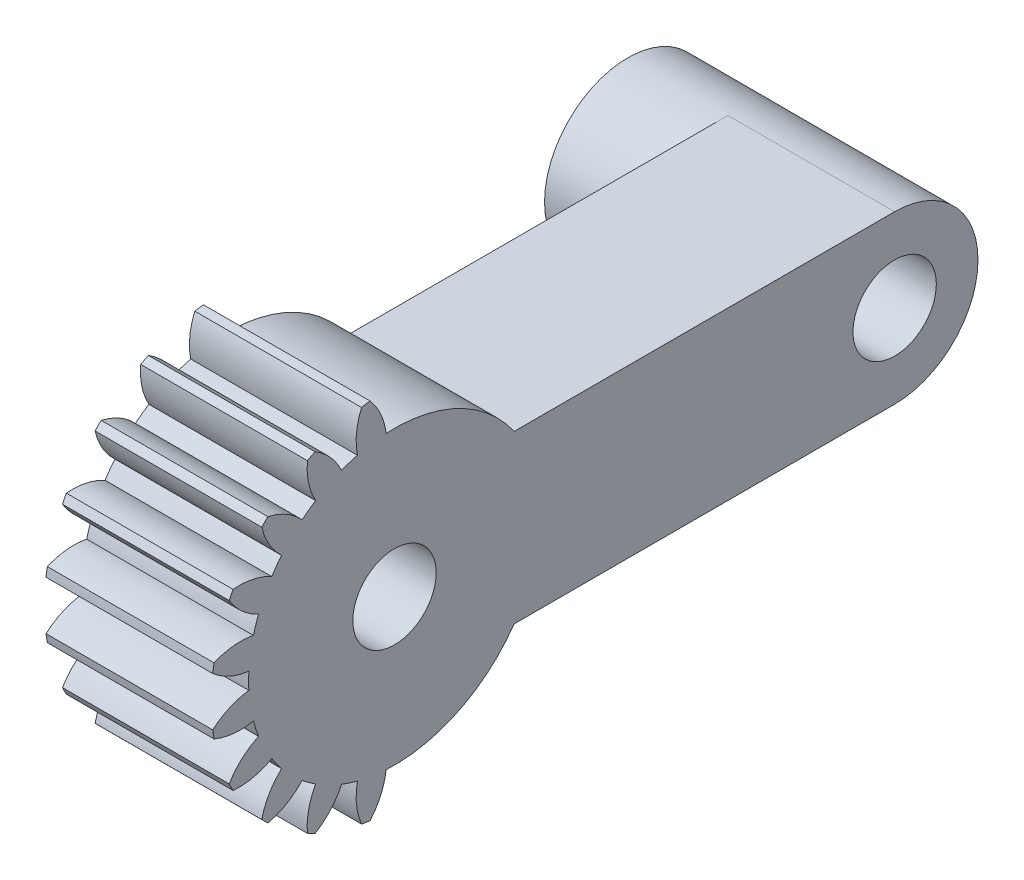
SolidWorks part; units mm, degrees
ref_plane "Front Plane" through (0, 0, 0) normal (0, 0, 1) x (1, 0, 0)
ref_plane "Top Plane" through (0, 0, 0) normal (0, 1, 0) x (1, 0, 0)
ref_plane "Right Plane" through (0, 0, 0) normal (1, 0, 0) x (0, 0, -1)
ref_plane "Plane1" through (4.0439, 0, 0) normal (1, 0, 0) x (0, 0, -1)
sketch "Sketch1" plane through (4.0439, 0, 0) normal (1, 0, 0) x (0, 0, -1)
  circle A0 centre (0.8725, -1.1221) radius 2.5
  arc A1 (-10.0295, 0.3429) -> (-7.8622, -0.6222) centre (-7.392, 3.3501) ccw
  arc A2 (-7.8622, -0.6222) -> (-7.8622, -1.622) centre (0.8725, -1.1221) ccw
  arc A3 (-7.8622, -1.622) -> (-10.0295, -2.587) centre (-7.392, -5.5943) ccw
  arc A4 (-10.0295, -2.587) -> (-9.9487, -3.0977) centre (0.8725, -1.1221) ccw
  arc A5 (-9.9487, -3.0977) -> (-7.5892, -3.3458) centre (-8.3695, 0.5774) ccw
  arc A6 (-7.5892, -3.3458) -> (-7.2802, -4.2967) centre (0.8725, -1.1221) ccw
  arc A7 (-7.2802, -4.2967) -> (-9.0433, -5.8842) centre (-5.6055, -7.9292) ccw
  arc A8 (-9.0433, -5.8842) -> (-8.8085, -6.3449) centre (0.8725, -1.1221) ccw
  arc A9 (-8.8085, -6.3449) -> (-6.4879, -5.8518) centre (-8.4423, -2.3617) ccw
  arc A10 (-6.4879, -5.8518) -> (-5.9002, -6.6607) centre (0.8725, -1.1221) ccw
  arc A11 (-5.9002, -6.6607) -> (-7.0864, -8.7153) centre (-3.185, -9.5979) ccw
  arc A12 (-7.0864, -8.7153) -> (-6.7207, -9.0809) centre (0.8725, -1.1221) ccw
  arc A13 (-6.7207, -9.0809) -> (-4.6661, -7.8948) centre (-7.6033, -5.1795) ccw
  arc A14 (-4.6661, -7.8948) -> (-3.8572, -8.4825) centre (0.8725, -1.1221) ccw
  arc A15 (-3.8572, -8.4825) -> (-4.3504, -10.8031) centre (-0.3672, -10.4369) ccw
  arc A16 (-4.3504, -10.8031) -> (-3.8897, -11.0378) centre (0.8725, -1.1221) ccw
  arc A17 (-3.8897, -11.0378) -> (-2.3022, -9.2748) centre (-5.9347, -7.6001) ccw
  arc A18 (-2.3022, -9.2748) -> (-1.3512, -9.5838) centre (0.8725, -1.1221) ccw
  arc A19 (-1.3512, -9.5838) -> (-1.1032, -11.9432) centre (2.5719, -10.3641) ccw
  arc A20 (-1.1032, -11.9432) -> (-0.5925, -12.0241) centre (0.8725, -1.1221) ccw
  arc A21 (-0.5925, -12.0241) -> (0.3725, -9.8568) centre (-3.5997, -9.3866) ccw
  arc A22 (0.3725, -9.8568) -> (1.3724, -9.8568) centre (0.8725, -1.1221) ccw
  arc A23 (1.3724, -9.8568) -> (2.3374, -12.0241) centre (5.3447, -9.3866) ccw
  arc A24 (2.3374, -12.0241) -> (2.8481, -11.9432) centre (0.8725, -1.1221) ccw
  arc A25 (2.8481, -11.9432) -> (3.0962, -9.5838) centre (-0.827, -10.3641) ccw
  arc A26 (3.0962, -9.5838) -> (4.0471, -9.2748) centre (0.8725, -1.1221) ccw
  arc A27 (4.0471, -9.2748) -> (5.6346, -11.0378) centre (7.6796, -7.6001) ccw
  arc A28 (5.6346, -11.0378) -> (6.0953, -10.8031) centre (0.8725, -1.1221) ccw
  arc A29 (6.0953, -10.8031) -> (5.6022, -8.4825) centre (2.1121, -10.4369) ccw
  arc A30 (5.6022, -8.4825) -> (6.411, -7.8948) centre (0.8725, -1.1221) ccw
  arc A31 (6.411, -7.8948) -> (8.4657, -9.0809) centre (9.3483, -5.1795) ccw
  arc A32 (8.4657, -9.0809) -> (8.8313, -8.7153) centre (0.8725, -1.1221) ccw
  arc A33 (8.8313, -8.7153) -> (7.6451, -6.6607) centre (4.9299, -9.5979) ccw
  arc A34 (7.6451, -6.6607) -> (8.2328, -5.8518) centre (0.8725, -1.1221) ccw
  arc A35 (8.2328, -5.8518) -> (10.5535, -6.3449) centre (10.1873, -2.3617) ccw
  arc A36 (10.5535, -6.3449) -> (10.7882, -5.8842) centre (0.8725, -1.1221) ccw
  arc A37 (10.7882, -5.8842) -> (9.0252, -4.2967) centre (7.3505, -7.9292) ccw
  arc A38 (9.0252, -4.2967) -> (9.3342, -3.3458) centre (0.8725, -1.1221) ccw
  arc A39 (9.3342, -3.3458) -> (11.6936, -3.0977) centre (10.1144, 0.5774) ccw
  arc A40 (11.6936, -3.0977) -> (11.7745, -2.587) centre (0.8725, -1.1221) ccw
  arc A41 (11.7745, -2.587) -> (9.6072, -1.622) centre (9.137, -5.5943) ccw
  arc A42 (9.6072, -1.622) -> (9.6072, -0.6222) centre (0.8725, -1.1221) ccw
  arc A43 (9.6072, -0.6222) -> (11.7745, 0.3429) centre (9.137, 3.3501) ccw
  arc A44 (11.7745, 0.3429) -> (11.6936, 0.8536) centre (0.8725, -1.1221) ccw
  arc A45 (11.6936, 0.8536) -> (9.3342, 1.1016) centre (10.1144, -2.8215) ccw
  arc A46 (9.3342, 1.1016) -> (9.0252, 2.0526) centre (0.8725, -1.1221) ccw
  arc A47 (9.0252, 2.0526) -> (10.7882, 3.6401) centre (7.3505, 5.6851) ccw
  arc A48 (10.7882, 3.6401) -> (10.5535, 4.1008) centre (0.8725, -1.1221) ccw
  arc A49 (10.5535, 4.1008) -> (8.2328, 3.6076) centre (10.1873, 0.1176) ccw
  arc A50 (8.2328, 3.6076) -> (7.6451, 4.4165) centre (0.8725, -1.1221) ccw
  arc A51 (7.6451, 4.4165) -> (8.8313, 6.4711) centre (4.9299, 7.3537) ccw
  arc A52 (8.8313, 6.4711) -> (8.4657, 6.8368) centre (0.8725, -1.1221) ccw
  arc A53 (8.4657, 6.8368) -> (6.411, 5.6506) centre (9.3483, 2.9353) ccw
  arc A54 (6.411, 5.6506) -> (5.6022, 6.2383) centre (0.8725, -1.1221) ccw
  arc A55 (5.6022, 6.2383) -> (6.0953, 8.5589) centre (2.1121, 8.1927) ccw
  arc A56 (6.0953, 8.5589) -> (5.6346, 8.7937) centre (0.8725, -1.1221) ccw
  arc A57 (5.6346, 8.7937) -> (4.0471, 7.0306) centre (7.6796, 5.3559) ccw
  arc A58 (4.0471, 7.0306) -> (3.0962, 7.3396) centre (0.8725, -1.1221) ccw
  arc A59 (3.0962, 7.3396) -> (2.8481, 9.6991) centre (-0.827, 8.1199) ccw
  arc A60 (2.8481, 9.6991) -> (2.3374, 9.7799) centre (0.8725, -1.1221) ccw
  arc A61 (2.3374, 9.7799) -> (1.3724, 7.6126) centre (5.3447, 7.1424) ccw
  arc A62 (1.3724, 7.6126) -> (0.3725, 7.6126) centre (0.8725, -1.1221) ccw
  arc A63 (0.3725, 7.6126) -> (-0.5925, 9.7799) centre (-3.5997, 7.1424) ccw
  arc A64 (-0.5925, 9.7799) -> (-1.1032, 9.6991) centre (0.8725, -1.1221) ccw
  arc A65 (-1.1032, 9.6991) -> (-1.3512, 7.3396) centre (2.5719, 8.1199) ccw
  arc A66 (-1.3512, 7.3396) -> (-2.3022, 7.0306) centre (0.8725, -1.1221) ccw
  arc A67 (-2.3022, 7.0306) -> (-3.8897, 8.7937) centre (-5.9347, 5.3559) ccw
  arc A68 (-3.8897, 8.7937) -> (-4.3504, 8.5589) centre (0.8725, -1.1221) ccw
  arc A69 (-4.3504, 8.5589) -> (-3.8572, 6.2383) centre (-0.3672, 8.1927) ccw
  arc A70 (-3.8572, 6.2383) -> (-4.6661, 5.6506) centre (0.8725, -1.1221) ccw
  arc A71 (-4.6661, 5.6506) -> (-6.7207, 6.8368) centre (-7.6033, 2.9353) ccw
  arc A72 (-6.7207, 6.8368) -> (-7.0864, 6.4711) centre (0.8725, -1.1221) ccw
  arc A73 (-7.0864, 6.4711) -> (-5.9002, 4.4165) centre (-3.185, 7.3537) ccw
  arc A74 (-5.9002, 4.4165) -> (-6.4879, 3.6076) centre (0.8725, -1.1221) ccw
  arc A75 (-6.4879, 3.6076) -> (-8.8085, 4.1008) centre (-8.4423, 0.1176) ccw
  arc A76 (-8.8085, 4.1008) -> (-9.0433, 3.6401) centre (0.8725, -1.1221) ccw
  arc A77 (-9.0433, 3.6401) -> (-7.2802, 2.0526) centre (-5.6055, 5.6851) ccw
  arc A78 (-7.2802, 2.0526) -> (-7.5892, 1.1016) centre (0.8725, -1.1221) ccw
  arc A79 (-7.5892, 1.1016) -> (-9.9487, 0.8536) centre (-8.3695, -2.8215) ccw
  arc A80 (-9.9487, 0.8536) -> (-10.0295, 0.3429) centre (0.8725, -1.1221) ccw
extrude "Boss-Extrude1" add sketch "Sketch1" against normal blind 10
sketch "Sketch2" plane through (4.0439, 0, 0) normal (1, 0, 0) x (0, 0, -1)
  line L0 (0.8725, -1.1221) -> (30.8725, -1.1221) construction
  line L1 (0.8725, 3.8779) -> (30.8725, 3.8779)
  line L2 (0.8725, -6.1221) -> (30.8725, -6.1221)
  arc A0 (0.8725, 3.8779) -> (0.8725, -6.1221) centre (0.8725, -1.1221) ccw
  arc A1 (30.8725, -6.1221) -> (30.8725, 3.8779) centre (30.8725, -1.1221) ccw
  arc A2 (35.8678, -1.3374) -> (35.8678, -0.9067) centre (30.8725, -1.1221) ccw
  circle A3 centre (30.8725, -1.1221) radius 2.5
  point P3 (15.8725, -1.1221)
  dimension "D2" = 5
  dimension "D1" = 10
  dimension "D3" = 30
extrude "Boss-Extrude2" add sketch "Sketch2" against normal blind 10 contours L2 A1 L1 A0 A3 region at (4.0439, -1.1221, -15.0519)
sketch "Sketch3" plane through (-5.9561, 0, 0) normal (-1, 0, 0) x (0, 0, 1)
  circle A0 centre (-30.8725, -1.1221) radius 2.5
  circle A1 centre (-30.8725, -1.1221) radius 5
extrude "Boss-Extrude3" add sketch "Sketch3" along normal blind 6
sketch "Sketch4" plane through (4.0439, 0, 0) normal (1, 0, 0) x (0, 0, -1)
  circle A1 centre (0.8725, -1.1221) radius 2.5
  dimension "D1" = 5
extrude "Cut-Extrude1" cut sketch "Sketch4" against normal blind 5
sketch "Sketch5" plane through (4.0439, 0, 0) normal (1, 0, 0) x (0, 0, -1)
  circle A0 centre (0.8725, -1.1221) radius 9.5637
sketch "Sketch6" plane through (-0.9561, 0, 0) normal (1, 0, 0) x (0, 0, -1)
  circle A0 centre (0.8725, -1.1221) radius 1.5
  dimension "D1" = 3
extrude "Cut-Extrude2" cut sketch "Sketch6" against normal through all
sketch "Sketch7" plane through (-5.9561, 0, 0) normal (-1, 0, 0) x (0, 0, 1)
  circle A0 centre (-0.8725, -1.1221) radius 2.5
  dimension "D1" = 5
extrude "Cut-Extrude3" cut sketch "Sketch7" against normal blind 3
sketch "Sketch8" plane through (-5.9561, 0, 0) normal (-1, 0, 0) x (0, 0, 1)
  circle A0 centre (-0.8725, -1.1221) radius 2.5
  circle A1 centre (-0.8725, -1.1221) radius 4.5
  dimension "D1" = 2
  dimension "D2" = 5
extrude "Boss-Extrude4" add sketch "Sketch8" along normal blind 2
sketch "Sketch9" plane through (4.0439, 0, 0) normal (1, 0, 0) x (0, 0, -1)
  line L0 (11.3023, -6.1221) -> (8.052, -6.1221)
  line L2 (11.3023, 3.8779) -> (8.052, 3.8779)
  line L4 (0.8725, 7.6269) -> (0.8725, 10.4444)
  line L5 (0.8725, -9.8711) -> (0.8725, -12.6885)
  arc A0 (0.8725, -9.8711) -> (8.052, -6.1221) centre (0.8725, -1.1221) ccw
  arc A1 (0.8725, -12.6885) -> (11.3023, -6.1221) centre (0.8725, -1.1221) ccw
  arc A2 (11.3023, 3.8779) -> (0.8725, 10.4444) centre (0.8725, -1.1221) ccw
  arc A3 (8.052, 3.8779) -> (0.8725, 7.6269) centre (0.8725, -1.1221) ccw
extrude "Cut-Extrude4" cut sketch "Sketch9" against normal through all
